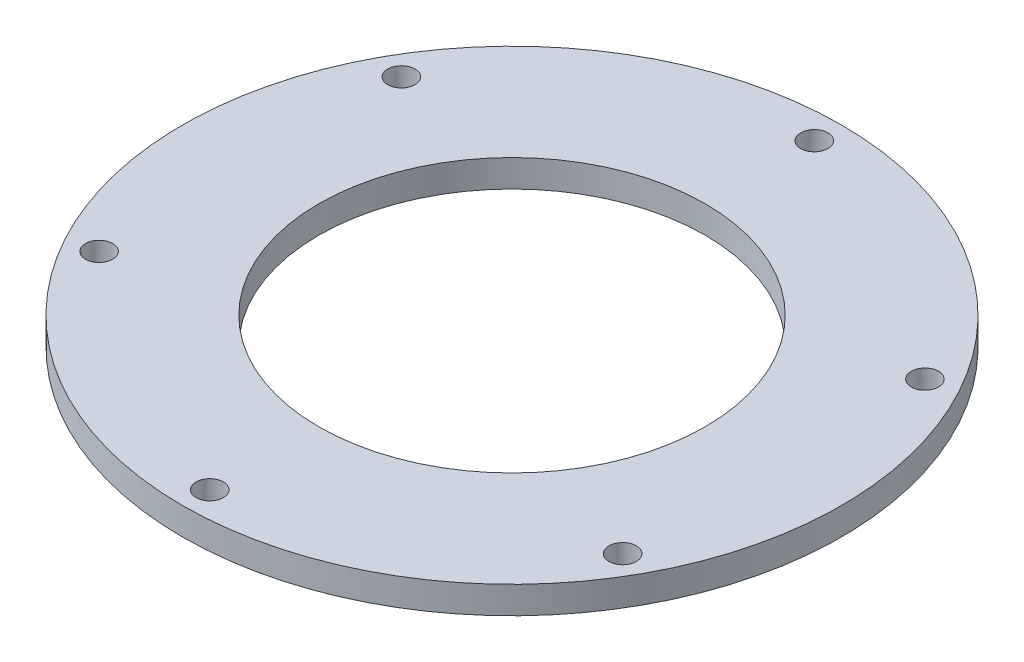
SolidWorks part; units mm, degrees
ref_plane "Front Plane" through (0, 0, 0) normal (0, 0, 1) x (1, 0, 0)
ref_plane "Top Plane" through (0, 0, 0) normal (0, 1, 0) x (1, 0, 0)
ref_plane "Right Plane" through (0, 0, 0) normal (1, 0, 0) x (0, 0, -1)
sketch "Sketch1" plane through (0, 0, 0) normal (0, 1, 0) x (1, 0, 0)
  circle A0 centre (0, 0) radius 21.25
  circle A1 centre (0, 0) radius 36.25
  dimension "D1" = 15
  dimension "D2" = 72.5
extrude "Boss-Extrude1" add sketch "Sketch1" along normal blind 3
sketch "Sketch2" plane through (0, 3, 0) normal (0, 1, 0) x (1, 0, 0)
  line L0 (0, 36.25) -> (0, 21.25) construction
  circle A3 centre (0, 0) radius 36.25 construction
  circle A4 centre (0, 0) radius 21.25 construction
  circle A5 centre (0, 33.25) radius 1.5
  dimension "D1" = 3
  dimension "D2" = 3
extrude "Cut-Extrude1" cut sketch "Sketch2" against normal through all both and the other way through all
pattern_circular "CirPattern1" count 6 every 60 about axis through (0, 3, 0) along (0, -1, 0) of "Cut-Extrude1"
